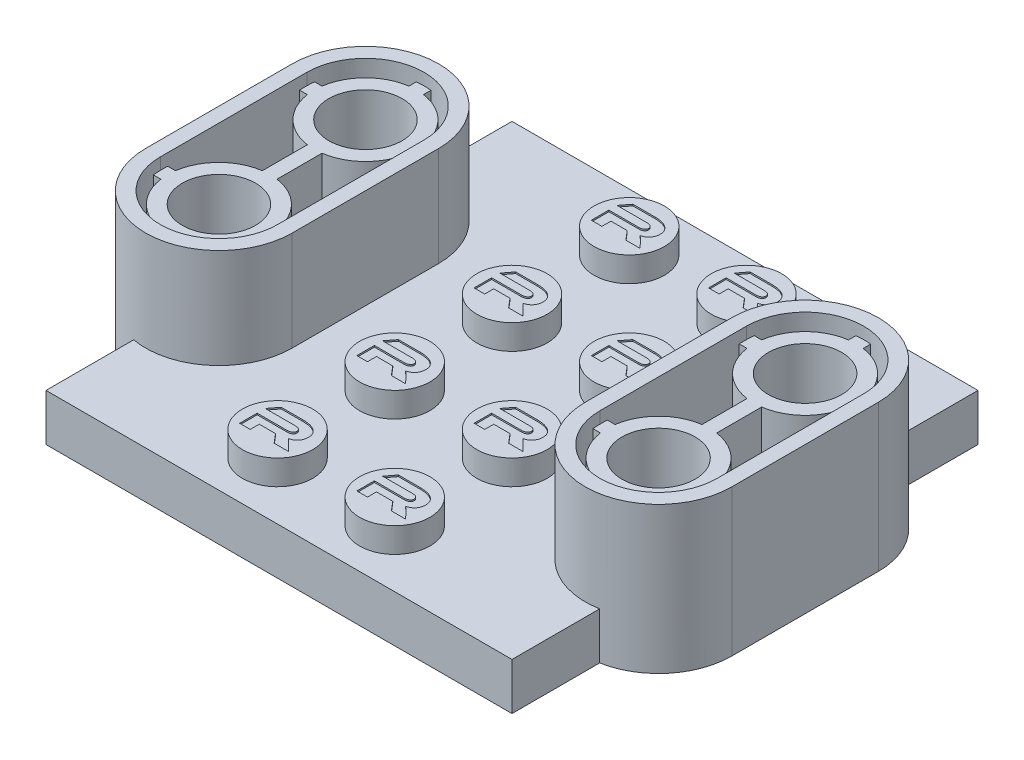
SolidWorks part; units mm, degrees
ref_plane "Front Plane" through (0, 0, 0) normal (0, 0, 1) x (1, 0, 0)
ref_plane "Top Plane" through (0, 0, 0) normal (0, 1, 0) x (1, 0, 0)
ref_plane "Right Plane" through (0, 0, 0) normal (1, 0, 0) x (0, 0, -1)
sketch "Sketch1" plane through (0, 0, 0) normal (0, 1, 0) x (1, 0, 0)
  line L0 (0, 0) -> (12, 0) construction
  line L1 (12, 0) -> (12, 12) construction
  circle A0 centre (12, 12) radius 2.4
  circle A1 centre (4, 12) radius 2.4
  circle A2 centre (-4, 12) radius 2.4
  circle A3 centre (-12, 12) radius 2.4
  circle A4 centre (4, 4) radius 2.4
  circle A5 centre (-4, 4) radius 2.4
  circle A6 centre (-12, 4) radius 2.4
  circle A7 centre (4, -4) radius 2.4
  circle A8 centre (-4, -4) radius 2.4
  circle A9 centre (-12, -4) radius 2.4
  circle A10 centre (4, -12) radius 2.4
  circle A11 centre (-4, -12) radius 2.4
  circle A12 centre (-12, -12) radius 2.4
  circle A13 centre (12, 4) radius 2.4
  circle A14 centre (12, -4) radius 2.4
  circle A15 centre (12, -12) radius 2.4
  point P5 (11.108, 12.3978)
  point P6 (-12.3146, 11.9018)
  point P37 (13.3676, 12)
  point P38 (-4.5726, 11.9795)
  point P39 (0, 0)
  dimension "D1" = 4.8
  dimension "D4" = 3.2
  dimension "D5" = 1.6
  dimension "D6" = 1.6
  dimension "D7" = 8
  dimension "D2" = 4
  dimension "D3" = 4
extrude "Boss-Extrude1" add sketch "Sketch1" along normal blind 1.7
sketch "Sketch2" plane through (0, 0, 0) normal (0, 1, 0) x (1, 0, 0)
  line L0 (-15.9, -15.9) -> (0, 0) construction
  line L1 (-15.9, 15.9) -> (15.9, 15.9)
  line L2 (-15.9, 15.9) -> (-15.9, -15.9)
  line L3 (-15.9, -15.9) -> (15.9, -15.9)
  line L4 (15.9, 15.9) -> (15.9, -15.9)
  line L5 (0, 0) -> (15.9, 15.9) construction
  dimension "D1" = 31.8
extrude "Boss-Extrude2" add sketch "Sketch2" against normal blind 3.2
sketch "Sketch3" plane through (0, 0, 0) normal (0, 1, 0) x (1, 0, 0)
  line L0 (0, 0) -> (20.2271, 0) construction
  line L1 (0, 0) -> (-18.7062, 0) construction
  line L2 (-5, 0) -> (-5, 17.8572) construction
  line L3 (5, 0) -> (5, 17.8572) construction
  line L4 (0, 0) -> (5, 3.7623) construction
  line L5 (5, 3.7623) -> (-5, 3.7623) construction
  line L6 (-5, 3.7623) -> (0, 0) construction
  line L7 (15, 0) -> (15, 17.8572) construction
  line L8 (-15, 0) -> (-15, 19.1796) construction
  line L9 (-19.013, 5) -> (21.5759, 5) construction
  line L10 (-18.7062, -5) -> (20.678, -5) construction
  line L11 (-20, 18.1776) -> (-20, -10.953) construction
  line L12 (20, 15.9147) -> (20, -9.3007) construction
  line L13 (22.9445, -8) -> (-25.8186, -8) construction
  line L14 (23.2798, 8) -> (-24.9395, 8) construction
  circle A2 centre (-15, 5) radius 2.5
  circle A4 centre (15, 5) radius 2.5
  circle A5 centre (-15, -5) radius 2.5
  circle A6 centre (15, -5) radius 2.5
  circle A7 centre (-12, 12) radius 2.4 construction
  circle A8 centre (-12, -12) radius 2.4 construction
  circle A9 centre (-15, 5) radius 3.5
  circle A10 centre (-12, 12) radius 3.9
  dimension "D6" = 5
  dimension "D9" = 1.6
  dimension "D10" = 1.6
  dimension "D11" = 1
  dimension "D1" = 10
  dimension "D2" = 10
  dimension "D3" = 10
  dimension "D4" = 5
  dimension "D5" = 10
  dimension "D7" = 40
  dimension "D8" = 20
sketch "Sketch4" plane through (0, 0, 0) normal (0, 1, 0) x (1, 0, 0)
  circle A0 centre (12, -4) radius 2.4 construction
  circle A1 centre (12, 4) radius 2.4 construction
  circle A2 centre (-12, -4) radius 2.4 construction
  circle A3 centre (-12, 4) radius 2.4 construction
  circle A4 centre (12, -4) radius 2.4
  circle A5 centre (12, 4) radius 2.4
  circle A6 centre (-12, -4) radius 2.4
  circle A7 centre (-12, 4) radius 2.4
extrude "Cut-Extrude1" cut sketch "Sketch4" along normal blind 8.2
sketch "Sketch5" plane through (0, -3.2, 0) normal (0, -1, 0) x (1, 0, 0)
  line L0 (-20, 5) -> (-20, -5)
  line L1 (20, 5) -> (20, -5)
  line L2 (-20, -18.1776) -> (-20, 10.953) construction
  circle A0 centre (-15, 5) radius 5
  circle A1 centre (-15, -5) radius 5
  circle A2 centre (15, 5) radius 5
  circle A3 centre (15, -5) radius 5
  point P16 (20, -5)
  point P17 (-20, -5)
  line M4 (-15.9, 15.9) -> (-15.9, -15.9)
  line M6 (15.9, -15.9) -> (15.9, 15.9)
  dimension "D1" = 10
extrude "Boss-Extrude3" add sketch "Sketch5" against normal up to surface (3.2 mm away) contours A0 M4 | A1 A0 L0 M4 | A1 M4 | A2 M6 | A3 L1 A2 M6 | A3 M6 region at (-18.8978, -3.2, 0) region at (-17.6161, -3.2, 5) region at (-17.6161, -3.2, -5) region at (17.6161, -3.2, 5) region at (18.8978, -3.2, 0) region at (17.6161, -3.2, -5) up to face at (12, 0, 14.4)
sketch "Sketch6" plane through (0, -3.2, 0) normal (0, -1, 0) x (1, 0, 0)
  line L17 (-14.9, -8.9987) -> (-14.9, -14.9)
  line L18 (-14.9, -14.9) -> (14.9, -14.9)
  line L19 (14.9, -14.9) -> (14.9, -8.9987)
  line L20 (19, -5) -> (19, 5)
  line L21 (14.9, 8.9987) -> (14.9, 14.9)
  line L22 (14.9, 14.9) -> (-14.9, 14.9)
  line L23 (-14.9, 14.9) -> (-14.9, 8.9987)
  line L24 (-19, 5) -> (-19, -5)
  line L25 (-14.9, -8.9987) -> (-14.9, -14.9)
  line L26 (-14.9, -14.9) -> (14.9, -14.9)
  line L27 (14.9, -14.9) -> (14.9, -8.9987)
  line L28 (19, -5) -> (19, 5)
  line L29 (14.9, 8.9987) -> (14.9, 14.9)
  line L30 (14.9, 14.9) -> (-14.9, 14.9)
  line L31 (-14.9, 14.9) -> (-14.9, 8.9987)
  line L32 (-19, 5) -> (-19, -5)
  circle A0 centre (-15, -5) radius 2.5 construction
  circle A1 centre (15, -5) radius 2.5 construction
  circle A2 centre (15, 5) radius 2.5 construction
  circle A3 centre (-15, 5) radius 2.5 construction
  circle A4 centre (-15, -5) radius 2.5
  circle A5 centre (15, -5) radius 2.5
  circle A6 centre (15, 5) radius 2.5
  circle A7 centre (-15, 5) radius 2.5
  circle A12 centre (-15, 5) radius 3.5
  circle A13 centre (15, 5) radius 3.5
  circle A14 centre (15, -5) radius 3.5
  circle A15 centre (-15, -5) radius 3.5
  arc A16 (14.9, -8.9987) -> (19, -5) centre (15, -5) ccw
  arc A17 (19, 5) -> (14.9, 8.9987) centre (15, 5) ccw
  arc A18 (-14.9, 8.9987) -> (-19, 5) centre (-15, 5) ccw
  arc A19 (-19, -5) -> (-14.9, -8.9987) centre (-15, -5) ccw
  arc A20 (14.9, -8.9987) -> (19, -5) centre (15, -5) ccw
  arc A21 (19, 5) -> (14.9, 8.9987) centre (15, 5) ccw
  arc A22 (-14.9, 8.9987) -> (-19, 5) centre (-15, 5) ccw
  arc A23 (-19, -5) -> (-14.9, -8.9987) centre (-15, -5) ccw
  dimension "D1" = 1
  dimension "D2" = 1
extrude "Cut-Extrude2" cut sketch "Sketch6" against normal blind 2.1 contours L32 A23 L25 L26 L27 A20 L28 A21 L29 L30 L31 A22 A12 A13 A14 A15 region at (0, -3.2, 0)
sketch "Sketch7" plane through (0, -3.2, 0) normal (0, -1, 0) x (1, 0, 0)
  circle A0 centre (-15, 5) radius 2.5 construction
  circle A1 centre (-15, 5) radius 2.5
  circle A2 centre (-15, -5) radius 2.5 construction
  circle A3 centre (15, -5) radius 2.5 construction
  circle A4 centre (15, 5) radius 2.5 construction
  circle A5 centre (-15, -5) radius 2.5
  circle A6 centre (15, -5) radius 2.5
  circle A7 centre (15, 5) radius 2.5
extrude "Cut-Extrude3" cut sketch "Sketch7" against normal blind 13.5
sketch "Sketch8" plane through (0, -3.2, 0) normal (0, -1, 0) x (1, 0, 0)
  circle A0 centre (-15, -5) radius 3.5 construction
  circle A1 centre (15, -5) radius 3.5 construction
  circle A2 centre (15, 5) radius 3.5 construction
  circle A3 centre (-15, 5) radius 3.5 construction
  circle A4 centre (-15, -5) radius 3.5
  circle A5 centre (15, -5) radius 3.5
  circle A6 centre (15, 5) radius 3.5
  circle A7 centre (-15, 5) radius 3.5
extrude "Cut-Extrude4" cut sketch "Sketch8" against normal blind 0.8
sketch "Sketch9" plane through (0, 0, 0) normal (0, 1, 0) x (1, 0, 0)
  circle A0 centre (15, 5) radius 2.5 construction
  circle A1 centre (15, -5) radius 2.5 construction
  circle A2 centre (-15, -5) radius 2.5 construction
  circle A3 centre (-15, 5) radius 2.5 construction
  circle A4 centre (15, 5) radius 2.5
  circle A5 centre (15, -5) radius 2.5
  circle A6 centre (-15, -5) radius 2.5
  circle A7 centre (-15, 5) radius 2.5
  circle A8 centre (15, 5) radius 3.5
  circle A9 centre (15, -5) radius 3.5
  circle A10 centre (-15, -5) radius 3.5
  circle A11 centre (-15, 5) radius 3.5
  dimension "D1" = 1
extrude "Boss-Extrude4" add sketch "Sketch9" along normal offset from surface (6 mm away) 8.4 up to face at (-15, -2.4, 1.5)
sketch "Sketch10" plane through (0, 0, 0) normal (0, 1, 0) x (1, 0, 0)
  line L0 (-18.7062, -5) -> (20.678, -5) construction
  line L1 (-19.013, 5) -> (21.5759, 5) construction
  line L2 (-20, 5) -> (-20, -5)
  line L3 (-10, 5) -> (-10, -5)
  line L4 (-19, 5) -> (-19, -5)
  line L5 (-11, 5) -> (-11, -5)
  line L6 (-15.5, 8.9686) -> (-15.5, -1.5359)
  line L7 (-14.5, 8.9686) -> (-14.5, -8.9686)
  line L8 (-15.5, -1.5359) -> (-15.5, -8.9686)
  line L9 (-19, -4.5) -> (-11, -4.5)
  line L10 (-18.9686, -5.5) -> (-11.0314, -5.5)
  line L11 (-18.9686, 5.5) -> (-11.0314, 5.5)
  line L12 (-19, 4.5) -> (-11, 4.5)
  line L13 (-15, 0) -> (-15, 19.1796) construction
  arc A0 (-20, -5) -> (-15.9, -9.9183) centre (-15, -5) ccw construction
  arc A1 (-15.9, 9.9183) -> (-20, 5) centre (-15, 5) ccw construction
  arc A2 (-20, -5) -> (-10, -5) centre (-15, -5) ccw
  arc A3 (-10, 5) -> (-20, 5) centre (-15, 5) ccw
  arc A4 (-19, -5) -> (-11, -5) centre (-15, -5) ccw
  arc A5 (-11, 5) -> (-19, 5) centre (-15, 5) ccw
  circle A6 centre (-15, -5) radius 3.5 construction
  circle M15 centre (-15, -5) radius 3.5
  arc M30 (-15.9, 9.9183) -> (-20, 5) centre (-15, 5) ccw
  line M31 (-20, 5) -> (-20, -5)
  arc M32 (-20, -5) -> (-15.9, -9.9183) centre (-15, -5) ccw
  circle M42 centre (-15, 5) radius 3.5
  dimension "D3" = 1
  dimension "D2" = 0.5
  dimension "D4" = 0.5
  dimension "D5" = 1
  dimension "D6" = 0.5
  dimension "D7" = 1
  dimension "D1" = 1
extrude "Boss-Extrude5" add sketch "Sketch10" along normal offset from surface (6.8 mm away) 10 contours L3 A3 A2 A5 L5 A4 L4 M30 M31 M32 | L7 A5 L6 M42 | L5 A5 L11 L12 M42 | L11 A5 L4 L12 M42 | L4 A4 L10 L9 M15 | L10 A4 L5 L9 M15 | L8 A4 L7 M15 | L7 L6 M42 M15 region at (-18.6688, 0, -8.0584) region at (-18.7414, 0, -4.9961) region at (-18.7414, 0, 4.9961) region at (-15, 0, -8.7388) region at (-15, 0, 0) region at (-11.2586, 0, -4.9961) region at (-15, 0, 8.7388) region at (-11.2586, 0, 4.9961) up to face at (0, -3.2, 0)
mirror "Mirror1" about plane through (0, 0, 0) normal (1, 0, 0) of "Boss-Extrude5"
sketch "Sketch11" plane through (0, 6, 0) normal (0, 1, 0) x (1, 0, 0)
  line L2 (19, 5) -> (19, -5) construction
  line L3 (19, 5) -> (19, -5)
  line L6 (-19, -5) -> (-19, 5) construction
  line L7 (-19, -5) -> (-19, 5)
  line L9 (-11, 5) -> (-11, -5)
  line L10 (11, 5) -> (11, -5)
  circle A0 centre (-15, 5) radius 4
  circle A1 centre (-15, -5) radius 4
  circle A2 centre (15, -5) radius 4
  circle A3 centre (15, 5) radius 4
  arc M4 (-11.5359, 5.5) -> (-14.5, 8.4641) centre (-15, 5) ccw
  arc M5 (-14.5, 8.4641) -> (-15.5, 8.4641) centre (-15, 5) ccw
  arc M6 (-15.5, 8.4641) -> (-18.4641, 5.5) centre (-15, 5) ccw
  arc M7 (-18.4641, 5.5) -> (-18.4641, 4.5) centre (-15, 5) ccw
  arc M8 (-18.4641, 4.5) -> (-15.5, 1.5359) centre (-15, 5) ccw
  arc M9 (-15.5, 1.5359) -> (-14.5, 1.5359) centre (-15, 5) ccw
extrude "Cut-Extrude5" cut sketch "Sketch11" along normal blind 10 contours A0 M4 M9 M8 M7 M6 M5 | A1 | A1 L9 A0 L7 | A3 L10 A2 L3 | A3 | A2 region at (15, 6, -5) region at (15, 6, 0) region at (15, 6, 5) region at (-15, 6, 0) region at (-15, 6, 5) region at (-15, 6, -5)
sketch "Sketch12" plane through (0, -3.2, 0) normal (0, -1, 0) x (1, 0, 0)
  line L2 (-10, -5) -> (-10, 5)
  line L3 (-20, 5) -> (-20, -5)
  line L4 (-10, -5) -> (-10, 5)
  line L5 (-20, 5) -> (-20, -5)
  line L6 (-19, 5) -> (-19, -5)
  line L7 (-11, -5) -> (-11, 5)
  line L8 (-19, 5) -> (-19, -5)
  line L9 (-11, -5) -> (-11, 5)
  line L11 (10, 5) -> (10, -5)
  line L12 (20, -5) -> (20, 5)
  line L13 (10, 5) -> (10, -5)
  line L14 (20, -5) -> (20, 5)
  line L15 (19, -5) -> (19, 5)
  line L16 (11, 5) -> (11, -5)
  line L17 (19, -5) -> (19, 5)
  line L18 (11, 5) -> (11, -5)
  arc A2 (-20, -5) -> (-10, -5) centre (-15, -5) ccw
  arc A3 (-10, 5) -> (-20, 5) centre (-15, 5) ccw
  arc A4 (-20, -5) -> (-10, -5) centre (-15, -5) ccw
  arc A5 (-10, 5) -> (-20, 5) centre (-15, 5) ccw
  arc A6 (-19, -5) -> (-11, -5) centre (-15, -5) ccw
  arc A7 (-11, 5) -> (-19, 5) centre (-15, 5) ccw
  arc A8 (-19, -5) -> (-11, -5) centre (-15, -5) ccw
  arc A9 (-11, 5) -> (-19, 5) centre (-15, 5) ccw
  arc A10 (10, -5) -> (20, -5) centre (15, -5) ccw
  arc A11 (20, 5) -> (10, 5) centre (15, 5) ccw
  arc A12 (10, -5) -> (20, -5) centre (15, -5) ccw
  arc A13 (20, 5) -> (10, 5) centre (15, 5) ccw
  arc A14 (11, -5) -> (19, -5) centre (15, -5) ccw
  arc A15 (19, 5) -> (11, 5) centre (15, 5) ccw
  arc A16 (11, -5) -> (19, -5) centre (15, -5) ccw
  arc A17 (19, 5) -> (11, 5) centre (15, 5) ccw
  dimension "D1" = 0
  dimension "D2" = 0
  dimension "D3" = 0
  dimension "D4" = 0
extrude "Boss-Extrude6" add sketch "Sketch12" against normal up to surface (2.1 mm away) up to face at (-15, -1.1, 1.5)
sketch "Sketch14" plane through (0, -2.4, 0) normal (0, -1, 0) x (1, 0, 0)
  line L18 (-11.0314, 5.5) -> (-11.5359, 5.5)
  line L19 (-11, 4.5) -> (-11, 5)
  line L20 (-11.5359, 4.5) -> (-11, 4.5)
  line L21 (-14.5, -1.5359) -> (-14.5, 1.5359)
  line L22 (-11, -4.5) -> (-11.5359, -4.5)
  line L23 (-11, -5) -> (-11, -4.5)
  line L24 (-11.5359, -5.5) -> (-11.0314, -5.5)
  line L25 (-14.5, -8.9686) -> (-14.5, -8.4641)
  line L26 (-15.5, -8.4641) -> (-15.5, -8.9686)
  line L27 (-18.9686, -5.5) -> (-18.4641, -5.5)
  line L28 (-19, -4.5) -> (-19, -5)
  line L29 (-18.4641, -4.5) -> (-19, -4.5)
  line L30 (-15.5, 1.5359) -> (-15.5, -1.5359)
  line L31 (-19, 4.5) -> (-18.4641, 4.5)
  line L32 (-19, 5) -> (-19, 4.5)
  line L33 (-18.4641, 5.5) -> (-18.9686, 5.5)
  line L34 (-15.5, 8.9686) -> (-15.5, 8.4641)
  line L35 (-14.5, 8.4641) -> (-14.5, 8.9686)
  line L36 (-11.0314, 5.5) -> (-11.5359, 5.5)
  line L37 (-11, 4.5) -> (-11, 5)
  line L38 (-11.5359, 4.5) -> (-11, 4.5)
  line L39 (-14.5, -1.5359) -> (-14.5, 1.5359)
  line L40 (-11, -4.5) -> (-11.5359, -4.5)
  line L41 (-11, -5) -> (-11, -4.5)
  line L42 (-11.5359, -5.5) -> (-11.0314, -5.5)
  line L43 (-14.5, -8.9686) -> (-14.5, -8.4641)
  line L44 (-15.5, -8.4641) -> (-15.5, -8.9686)
  line L45 (-18.9686, -5.5) -> (-18.4641, -5.5)
  line L46 (-19, -4.5) -> (-19, -5)
  line L47 (-18.4641, -4.5) -> (-19, -4.5)
  line L48 (-15.5, 1.5359) -> (-15.5, -1.5359)
  line L49 (-19, 4.5) -> (-18.4641, 4.5)
  line L50 (-19, 5) -> (-19, 4.5)
  line L51 (-18.4641, 5.5) -> (-18.9686, 5.5)
  line L52 (-15.5, 8.9686) -> (-15.5, 8.4641)
  line L53 (-14.5, 8.4641) -> (-14.5, 8.9686)
  circle A0 centre (-15, 5) radius 2.5 construction
  circle A1 centre (-15, -5) radius 2.5 construction
  circle A2 centre (-15, 5) radius 2.5
  circle A3 centre (-15, -5) radius 2.5
  arc A14 (-11.5359, 5.5) -> (-14.5, 8.4641) centre (-15, 5) ccw
  arc A15 (-11, 5) -> (-11.0314, 5.5) centre (-15, 5) ccw
  arc A16 (-14.5, 1.5359) -> (-11.5359, 4.5) centre (-15, 5) ccw
  arc A17 (-11.5359, -4.5) -> (-14.5, -1.5359) centre (-15, -5) ccw
  arc A18 (-11.0314, -5.5) -> (-11, -5) centre (-15, -5) ccw
  arc A19 (-14.5, -8.4641) -> (-11.5359, -5.5) centre (-15, -5) ccw
  arc A20 (-15.5, -8.9686) -> (-14.5, -8.9686) centre (-15, -5) ccw
  arc A21 (-18.4641, -5.5) -> (-15.5, -8.4641) centre (-15, -5) ccw
  arc A22 (-19, -5) -> (-18.9686, -5.5) centre (-15, -5) ccw
  arc A23 (-15.5, -1.5359) -> (-18.4641, -4.5) centre (-15, -5) ccw
  arc A24 (-18.4641, 4.5) -> (-15.5, 1.5359) centre (-15, 5) ccw
  arc A25 (-18.9686, 5.5) -> (-19, 5) centre (-15, 5) ccw
  arc A26 (-15.5, 8.4641) -> (-18.4641, 5.5) centre (-15, 5) ccw
  arc A27 (-14.5, 8.9686) -> (-15.5, 8.9686) centre (-15, 5) ccw
  arc A28 (-11.5359, 5.5) -> (-14.5, 8.4641) centre (-15, 5) ccw
  arc A29 (-11, 5) -> (-11.0314, 5.5) centre (-15, 5) ccw
  arc A30 (-14.5, 1.5359) -> (-11.5359, 4.5) centre (-15, 5) ccw
  arc A31 (-11.5359, -4.5) -> (-14.5, -1.5359) centre (-15, -5) ccw
  arc A32 (-11.0314, -5.5) -> (-11, -5) centre (-15, -5) ccw
  arc A33 (-14.5, -8.4641) -> (-11.5359, -5.5) centre (-15, -5) ccw
  arc A34 (-15.5, -8.9686) -> (-14.5, -8.9686) centre (-15, -5) ccw
  arc A35 (-18.4641, -5.5) -> (-15.5, -8.4641) centre (-15, -5) ccw
  arc A36 (-19, -5) -> (-18.9686, -5.5) centre (-15, -5) ccw
  arc A37 (-15.5, -1.5359) -> (-18.4641, -4.5) centre (-15, -5) ccw
  arc A38 (-18.4641, 4.5) -> (-15.5, 1.5359) centre (-15, 5) ccw
  arc A39 (-18.9686, 5.5) -> (-19, 5) centre (-15, 5) ccw
  arc A40 (-15.5, 8.4641) -> (-18.4641, 5.5) centre (-15, 5) ccw
  arc A41 (-14.5, 8.9686) -> (-15.5, 8.9686) centre (-15, 5) ccw
  dimension "D1" = 0
extrude "Boss-Extrude7" add sketch "Sketch14" against normal up to surface (1.3 mm away) up to face at (-15, -1.1, -8.5)
mirror "Mirror2" about plane through (0, 0, 0) normal (1, 0, 0) of "Boss-Extrude7"
sketch "Sketch15" plane through (0, 0, 0) normal (0, 1, 0) x (1, 0, 0)
  circle A0 centre (12, -12) radius 2.4 construction
  circle A1 centre (-12, -12) radius 2.4 construction
  circle A2 centre (-12, 12) radius 2.4 construction
  circle A3 centre (12, 12) radius 2.4 construction
  circle A4 centre (12, -12) radius 2.4
  circle A5 centre (-12, -12) radius 2.4
  circle A6 centre (-12, 12) radius 2.4
  circle A7 centre (12, 12) radius 2.4
extrude "Cut-Extrude6" cut sketch "Sketch15" along normal blind 7
sketch "Sketch16" plane through (0, -1.1, 0) normal (0, -1, 0) x (1, 0, 0)
  line L0 (0, 14.4) -> (0, -14.9) construction
  line L1 (-14.9, -14.9) -> (14.9, -14.9) construction
  line L2 (-14.9, 14.4) -> (14.9, 14.4)
  line L3 (-14.9, 14.9) -> (-14.9, 9.999) construction
  line L4 (14.9, 9.999) -> (14.9, 14.9) construction
  line L5 (14.9, 14.4) -> (14.9, 14.9)
  line L6 (14.9, 14.9) -> (-14.9, 14.9)
  line L7 (-14.9, 14.9) -> (-14.9, 14.4)
  line L8 (14.9, -14.9) -> (14.9, -9.999) construction
  line L9 (-14.9, -14.9) -> (14.9, -14.9)
  line L10 (-14.9, -14.9) -> (-14.9, -14.4)
  line L11 (-14.9, -14.4) -> (14.9, -14.4)
  line L12 (14.9, -14.9) -> (14.9, -14.4)
  line L13 (-14.9, 14.9) -> (-14.9, 9.999) construction
  line L14 (-14.9, 14.9) -> (-14.9, 9.999)
  line L15 (-14.4, 14.4) -> (-14.4, 10.1811)
  line L16 (-8, 15.9) -> (-8, 2.9685) construction
  line L17 (-15.9, 15.9) -> (15.9, 15.9) construction
  line L18 (14.4, 14.4) -> (14.4, 10.1811)
  line L19 (-8, 2.9685) -> (-8, -17.0164) construction
  line L20 (0, 0) -> (-25.022, 0) construction
  line L21 (-14.4, -14.4) -> (-14.4, -10.1811)
  line L22 (-14.9, -14.9) -> (-14.9, -9.999)
  line L23 (-14.9, -14.9) -> (-14.9, -14.4)
  line L24 (14.4, -14.4) -> (14.4, -10.1811)
  circle A0 centre (-4, 4) radius 2.4 construction
  circle A1 centre (-4, -4) radius 2.4 construction
  circle A2 centre (-4, -12) radius 2.4 construction
  circle A3 centre (4, -12) radius 2.4 construction
  circle A4 centre (4, -4) radius 2.4 construction
  circle A5 centre (4, 4) radius 2.4 construction
  circle A6 centre (-4, 12) radius 2.4 construction
  circle A7 centre (4, 12) radius 2.4 construction
  circle A8 centre (-4, 4) radius 2.4 construction
  circle A9 centre (-4, -4) radius 2.4 construction
  circle A10 centre (-4, -12) radius 2.4 construction
  circle A11 centre (4, -12) radius 2.4 construction
  circle A12 centre (4, -4) radius 2.4 construction
  circle A13 centre (4, 4) radius 2.4 construction
  circle A14 centre (-4, 12) radius 2.4 construction
  circle A15 centre (4, 12) radius 2.4 construction
  circle A16 centre (0, 8) radius 3.2569
  circle A17 centre (0, 0) radius 3.2569
  circle A18 centre (0, -8) radius 3.2569
  circle A19 centre (0, 8) radius 2.5569
  circle A20 centre (0, 0) radius 2.5569
  circle A21 centre (0, -8) radius 2.5569
  circle A22 centre (-12, 12) radius 2.4 construction
  circle A23 centre (-15, 5) radius 5.2158
  circle A24 centre (-8, 8) radius 3.2569
  circle A25 centre (-8, 8) radius 2.5569
  circle A26 centre (15, 5) radius 5.2158
  circle A27 centre (8, 8) radius 2.5569
  circle A28 centre (8, 8) radius 3.2569
  circle A29 centre (-12, -12) radius 2.4 construction
  circle A30 centre (-8, -8) radius 2.5569
  circle A31 centre (-8, -8) radius 3.2569
  circle A32 centre (-15, -5) radius 5.2158
  circle A33 centre (-8, 0) radius 3.2569
  circle A34 centre (-8, 0) radius 2.5569
  circle A35 centre (8, -8) radius 2.5569
  circle A36 centre (8, -8) radius 3.2569
  circle A37 centre (15, -5) radius 5.2158
  circle A38 centre (8, 0) radius 2.5569
  circle A39 centre (8, 0) radius 3.2569
  arc M25 (10, 5) -> (14.9, 9.999) centre (15, 5) cw
  line M26 (14.9, 9.999) -> (14.9, 14.9)
  line M27 (14.9, 14.9) -> (-14.9, 14.9)
  line M28 (-14.9, 14.9) -> (-14.9, 9.999)
  arc M29 (-14.9, 9.999) -> (-10, 5) centre (-15, 5) cw
  line M30 (-10, 5) -> (-10, -5)
  arc M31 (-10, -5) -> (-14.9, -9.999) centre (-15, -5) cw
  line M32 (-14.9, -9.999) -> (-14.9, -14.9)
  line M33 (-14.9, -14.9) -> (14.9, -14.9)
  line M34 (14.9, -14.9) -> (14.9, -9.999)
  arc M35 (14.9, -9.999) -> (10, -5) centre (15, -5) cw
  line M36 (10, -5) -> (10, 5)
  dimension "D2" = 2
  dimension "D3" = 8
  dimension "D1" = 0.7
  dimension "D4" = 0.7
  dimension "D5" = 0.7
extrude "Boss-Extrude8" add sketch "Sketch16" along normal up to surface (2.1 mm away) contours L2 M28 M26 M27 | L18 A26 L2 M26 | A26 A28 M25 M26 | A28 A26 A27 | A28 A26 A27 M25 | A28 A26 M25 M36 | A27 A26 | A16 A19 | A25 A23 A24 | A23 L15 L2 M28 | A24 A23 L14 M29 | A25 A23 A24 M29 | A23 A25 | A24 A23 M29 M30 | A34 A33 M30 | A17 A20 | A39 A38 M36 | A31 A32 A30 | A18 A21 | A37 A36 A35 | L21 A32 L22 L11 | L11 M32 M33 M34 | A32 A31 M31 M32 | A32 A31 A30 M31 | A32 A30 | A32 A31 M30 M31 | A37 L24 L11 M34 | A36 A37 M34 M35 | A36 A37 A35 M35 | A37 A36 M36 M35 | A35 A37 region at (0, -1.1, 14.65) region at (-14.6497, -1.1, 12.301) region at (-14.6524, -1.1, 10.1625) region at (14.6497, -1.1, 12.301) region at (14.6524, -1.1, 10.1625) region at (-7.7179, -1.1, 11.1525) region at (-10.8779, -1.1, 8.1366) region at (-14.6497, -1.1, -12.301) region at (-14.8584, -1.1, -10.1069) region at (11.1914, -1.1, 8.4343) region at (10.7763, -1.1, 8.214) region at (-10.2731, -1.1, 7.0258) region at (-9.9112, -1.1, 4.6388) region at (-9.9112, -1.1, -4.6388) region at (0, -1.1, -14.65) region at (10.2731, -1.1, 7.0258) region at (9.9112, -1.1, 4.6388) region at (-6.6061, -1.1, 2.8506) region at (-10.3712, -1.1, -6.9838) region at (-10.7763, -1.1, -8.214) region at (14.6497, -1.1, -12.301) region at (-10.2731, -1.1, -7.0258) region at (9.9163, -1.1, 2.0817) region at (12.6796, -1.1, -9.6247) region at (9.9112, -1.1, -4.6388) region at (10.8779, -1.1, -8.1366) region at (5.0908, -1.1, -9.2468) region at (10.2731, -1.1, -7.0258) region at (-3.1647, -1.1, 8) region at (-3.1647, -1.1, 0) region at (-3.1647, -1.1, -8) up to face at (0, -3.2, 0)
sketch "Sketch17" plane through (0, -1.1, 0) normal (0, -1, 0) x (1, 0, 0)
  circle A0 centre (-4, 4) radius 2.4 construction
  circle A1 centre (-4, -4) radius 2.4 construction
  circle A2 centre (-4, -12) radius 2.4 construction
  circle A3 centre (4, -12) radius 2.4 construction
  circle A4 centre (4, -4) radius 2.4 construction
  circle A5 centre (4, 4) radius 2.4 construction
  circle A6 centre (-4, 12) radius 2.4 construction
  circle A7 centre (4, 12) radius 2.4 construction
  circle A8 centre (-4, 4) radius 2.4 construction
  circle A9 centre (-4, -4) radius 2.4 construction
  circle A10 centre (-4, -12) radius 2.4 construction
  circle A11 centre (4, -12) radius 2.4 construction
  circle A12 centre (4, -4) radius 2.4 construction
  circle A13 centre (4, 4) radius 2.4 construction
  circle A14 centre (-4, 12) radius 2.4 construction
  circle A15 centre (4, 12) radius 2.4 construction
  circle A16 centre (-4, 4) radius 1.1
  circle A17 centre (-4, -4) radius 1.1
  circle A18 centre (-4, -12) radius 1.1
  circle A19 centre (4, -12) radius 1.1
  circle A20 centre (4, -4) radius 1.1
  circle A21 centre (4, 4) radius 1.1
  circle A22 centre (-4, 12) radius 1.1
  circle A23 centre (4, 12) radius 1.1
  dimension "D1" = 1.3
extrude "Cut-Extrude7" cut sketch "Sketch17" against normal offset from surface (1.8 mm away) 1 up to face at (4, 1.7, 14.4)
sketch "Sketch18" plane through (0, -3.2, 0) normal (0, -1, 0) x (1, 0, 0)
  circle A0 centre (-8, 8) radius 2.5569
  circle A1 centre (-8, 0) radius 2.5569
  circle A2 centre (8, 0) radius 2.5569
  circle A3 centre (8, 8) radius 2.5569
  circle A4 centre (-8, -8) radius 2.5569
  circle A5 centre (8, -8) radius 2.5569
extrude "Cut-Extrude8" cut sketch "Sketch18" against normal up to surface (2.1 mm away) up to face at (4, -1.1, 2.9)
sketch "Sketch19" plane through (0, 1.7, 0) normal (0, 1, 0) x (1, 0, 0)
  line L0 (-5.8644, 11.0628) -> (-1.6, 11.0628) construction
  line L1 (-5.8644, 11.0628) -> (-5.8644, 9.0944) construction
  circle A2 centre (-4, 12) radius 1.9026 construction
  circle A3 centre (-4, 12) radius 2.4 construction
  text T0 "R" font "Ethnocentric Rg" height in points 9
  point P3 (-3.9366, 11.859)
  point P6 (-5.8853, 10.8951)
  point P10 (-5.8853, 10.979)
  point P11 (-5.8644, 11.0628)
extrude "Cut-Extrude9" cut sketch "Sketch19" against normal blind 0.1
pattern_linear "LPattern1" count 2 spacing 8 along (1, 0, 0) count 4 spacing 8 along (0, 0, 1) of "Cut-Extrude9"
